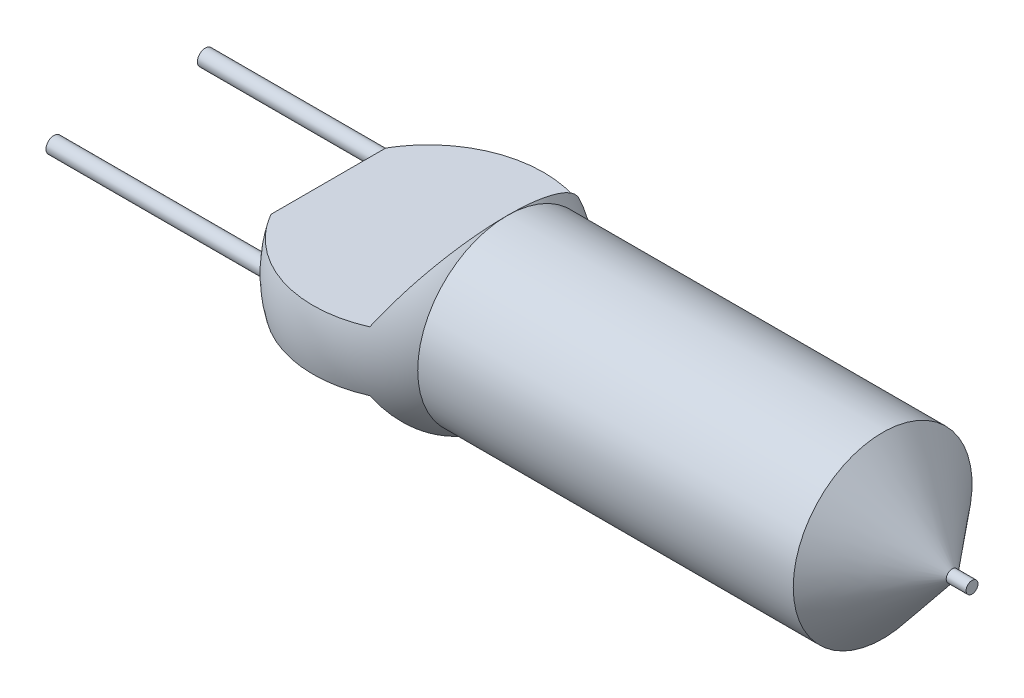
SolidWorks part; units mm, degrees
ref_plane "前视基准面" through (0, 0, 0) normal (0, 0, 1) x (1, 0, 0)
ref_plane "上视基准面" through (0, 0, 0) normal (0, 1, 0) x (1, 0, 0)
ref_plane "右视基准面" through (0, 0, 0) normal (1, 0, 0) x (0, 0, -1)
sketch "草图1" plane through (0, 0, 0) normal (0, 0, 1) x (1, 0, 0)
  line L0 (-53.4381, 0) -> (110.8055, 0) construction
  line L1 (0, 0) -> (0, 3.25)
  line L2 (9, 4.5) -> (27.9, 4.5)
  line L3 (27.9, 4.5) -> (31.4, 0.3)
  line L4 (31.4, 0.3) -> (32.4, 0.3)
  line L5 (32.4, 0.3) -> (32.4, 0)
  line L6 (0, 0) -> (32.4, 0)
  arc A0 (0, 3.25) -> (9, 4.5) centre (5.0382, 0) cw
  dimension "D2" = 4.5
  dimension "D1" = 3.25
  dimension "D3" = 27.9
  dimension "D4" = 9
  dimension "D5" = 1
  dimension "D6" = 32.4
  dimension "D7" = 0.3
revolve "旋转1" add sketch "草图1" angle 360 about L0
sketch "草图3" plane through (0, 0, 0) normal (0, 0, 1) x (1, 0, 0)
  line L0 (9, 4.5) -> (7.3916, 1.5)
  line L1 (7.3916, 1.5) -> (-2.8153, 1.5)
  line L2 (-2.8153, 1.5) -> (-2.8153, 8.9033)
  line L3 (-2.8153, 8.9033) -> (9, 8.9033)
  line L4 (9, 8.9033) -> (9, 4.5)
  line L5 (-7.3283, 0) -> (36.6351, 0) construction
  line L6 (9, -8.9033) -> (9, -4.5)
  line L7 (-2.8153, -8.9033) -> (9, -8.9033)
  line L8 (-2.8153, -1.5) -> (-2.8153, -8.9033)
  line L9 (7.3916, -1.5) -> (-2.8153, -1.5)
  line L10 (9, -4.5) -> (7.3916, -1.5)
  dimension "D1" = 3
extrude "切除-拉伸1" cut sketch "草图3" against normal blind 10 and the other way blind 10
sketch "草图2" plane through (0, 0, 0) normal (-1, 0, 0) x (0, 0, 1)
  line L0 (-10.605, 0) -> (9.6243, 0) construction
  line L1 (0, 4.6966) -> (0, -5.0809) construction
  circle A0 centre (-3.81, 0) radius 0.4
  circle A1 centre (3.81, 0) radius 0.4
  dimension "D1" = 0.8
  dimension "D2" = 7.62
extrude "凸台-拉伸1" add sketch "草图2" along normal blind 10 and the other way blind 4 separate body
